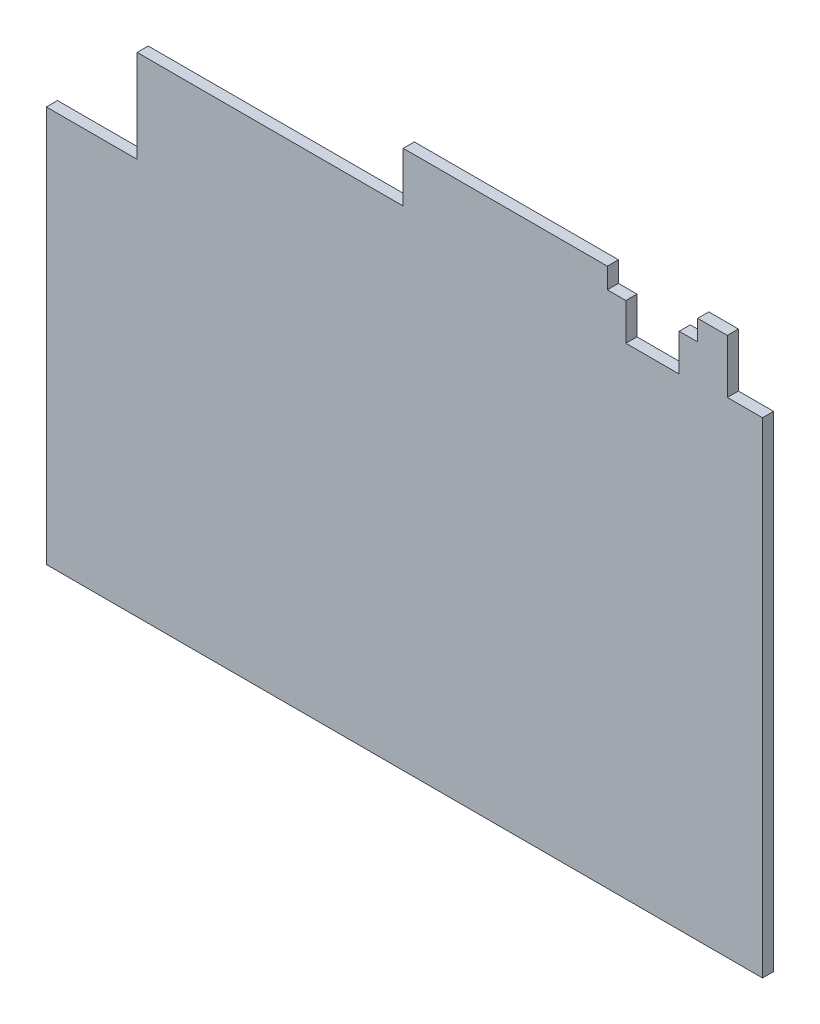
SolidWorks part; units mm, degrees
material "Pine"
ref_plane "Front Plane" through (0, 0, 0) normal (0, 0, 1) x (1, 0, 0)
ref_plane "Top Plane" through (0, 0, 0) normal (0, 1, 0) x (1, 0, 0)
ref_plane "Right Plane" through (0, 0, 0) normal (1, 0, 0) x (0, 0, -1)
sketch "Sketch1" plane through (0, 0, 0) normal (0, 0, 1) x (1, 0, 0)
  line L0 (28.5714, 236.0602) -> (28.5714, 237.0518)
  line L1 (28.5714, 277.1048) -> (28.5714, -22.8952) construction
  line L2 (28.5714, 237.0518) -> (5.4155, 237.0518)
  line L3 (5.4155, 237.0518) -> (4.5714, 268.1048)
  line L4 (4.5714, 268.1048) -> (-12.4286, 268.1048)
  line L5 (-12.4286, 268.1048) -> (-12.4286, 237.0518)
  line L6 (-12.4286, 237.0518) -> (-38.2166, 237.0518)
  line L7 (-38.2166, 237.0518) -> (-38.2166, 268.1048)
  line L8 (-221.4286, 268.1048) -> (28.5714, 268.1048) construction
  line L9 (-38.2166, 268.1048) -> (-171.4286, 268.1048)
  line L10 (-171.4286, 268.1048) -> (-171.4286, 241.1048)
  line L11 (-171.4286, 241.1048) -> (-370.1235, 241.1048)
  line L12 (-370.1235, 241.1048) -> (-370.1235, -22.8952)
  line L13 (-370.1235, -22.8952) -> (28.5714, -22.8952)
  line L14 (28.5714, -22.8952) -> (28.5714, 236.0602)
extrude "Boss-Extrude1" add sketch "Sketch1" along normal blind 6
sketch "Sketch2" plane through (0, 0, 6) normal (0, 0, 1) x (1, 0, 0)
  line L1 (-370.1235, 241.1048) -> (-315.1235, 241.1048)
  line L2 (-370.1235, 241.1048) -> (-370.1235, 191.1048)
  line L3 (-370.1235, 191.1048) -> (-315.1235, 191.1048)
  line L4 (-315.1235, 241.1048) -> (-315.1235, 191.1048)
  dimension "D1" = 55
  dimension "D2" = 50
extrude "Cut-Extrude1" cut sketch "Sketch2" against normal blind 10
sketch "Sketch3" plane through (0, 0, 6) normal (0, 0, 1) x (1, 0, 0)
  line L0 (4.5714, 268.1048) -> (-12.4286, 268.1048) construction
  line L1 (28.5714, -22.8952) -> (22.5714, -22.8952)
  line L2 (28.5714, -22.8952) -> (28.5714, 268.1048)
  line L3 (28.5714, 268.1048) -> (22.5714, 268.1048)
  line L4 (22.5714, -22.8952) -> (22.5714, 268.1048)
  line L5 (-171.4286, 241.1048) -> (-315.1235, 241.1048) construction
  line L6 (-370.1235, -22.8952) -> (-364.1235, -22.8952)
  line L7 (-370.1235, -22.8952) -> (-370.1235, 241.1048)
  line L8 (-370.1235, 241.1048) -> (-364.1235, 241.1048)
  line L9 (-364.1235, -22.8952) -> (-364.1235, 241.1048)
  dimension "D1" = 6
  dimension "D2" = 6
extrude "Cut-Extrude2" cut sketch "Sketch3" against normal blind 10
sketch "Sketch4" plane through (0, 0, 6) normal (0, 0, 1) x (1, 0, 0)
  line L1 (-38.2166, 268.1048) -> (-61.2166, 268.1048)
  line L2 (-38.2166, 268.1048) -> (-38.2166, 237.0518)
  line L3 (-38.2166, 237.0518) -> (-61.2166, 237.0518)
  line L4 (-61.2166, 268.1048) -> (-61.2166, 237.0518)
  line L5 (4.5714, 268.1048) -> (3.5714, 268.1048)
  line L6 (4.5714, 268.1048) -> (4.5714, 237.0518)
  line L7 (4.5714, 237.0518) -> (3.5714, 237.0518)
  line L8 (3.5714, 268.1048) -> (3.5714, 237.0518)
  dimension "D1" = 23
  dimension "D2" = 1
extrude "Cut-Extrude3" cut sketch "Sketch4" against normal blind 10
sketch "Sketch5" plane through (0, 0, 6) normal (0, 0, 1) x (1, 0, 0)
  line L1 (-61.2166, 237.0518) -> (-51.2166, 237.0518)
  line L2 (-61.2166, 237.0518) -> (-61.2166, 257.0518)
  line L3 (-61.2166, 257.0518) -> (-51.2166, 257.0518)
  line L4 (-51.2166, 237.0518) -> (-51.2166, 257.0518)
  line L5 (-12.4286, 237.0518) -> (-22.4286, 237.0518)
  line L6 (-12.4286, 237.0518) -> (-12.4286, 257.0518)
  line L7 (-12.4286, 257.0518) -> (-22.4286, 257.0518)
  line L8 (-22.4286, 237.0518) -> (-22.4286, 257.0518)
  dimension "D1" = 20
  dimension "D2" = 20
  dimension "D3" = 10
  dimension "D4" = 10
extrude "Boss-Extrude2" add sketch "Sketch5" against normal up to vertex (6 mm away) up to point (-61.2166, 268.1048, 0)
sketch "Sketch6" plane through (0, 0, 6) normal (0, 0, 1) x (1, 0, 0)
  line L1 (4.5714, 237.0518) -> (9.0632, 237.0518)
  line L2 (4.5714, 237.0518) -> (4.5714, 268.9907)
  line L3 (4.5714, 268.9907) -> (9.0632, 268.9907)
  line L4 (9.0632, 237.0518) -> (9.0632, 268.9907)
extrude "Cut-Extrude4" cut sketch "Sketch6" against normal blind 10
sketch "Sketch7" plane through (0, 0, 6) normal (0, 0, 1) x (1, 0, 0)
  line L0 (3.5714, 268.1048) -> (3.5714, 237.0518) construction
  line L1 (22.5714, 237.0518) -> (3.5714, 237.0518)
  line L2 (22.5714, 237.0518) -> (22.5714, 239.1018)
  line L3 (22.5714, 239.1018) -> (3.5714, 239.1018)
  line L4 (3.5714, 237.0518) -> (3.5714, 239.1018)
  dimension "D1" = 2.05
extrude "Boss-Extrude3" add sketch "Sketch7" against normal up to vertex (6 mm away) up to point (3.5714, 237.0518, 0)
